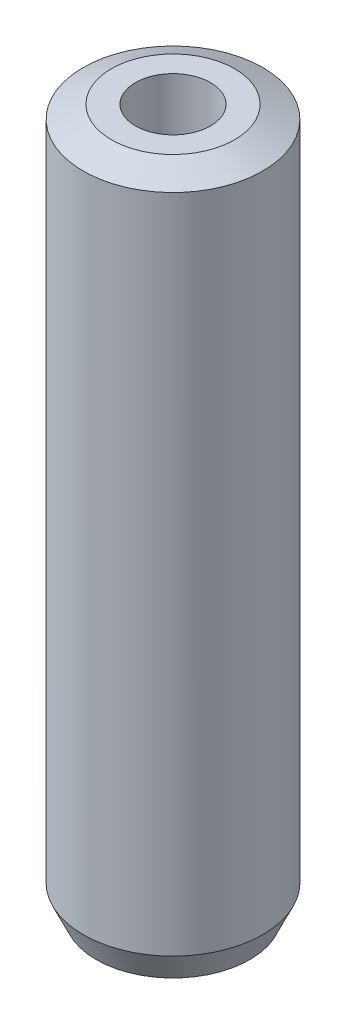
SolidWorks part; units mm, degrees
ref_plane "Front Plane" through (0, 0, 0) normal (0, 0, 1) x (1, 0, 0)
ref_plane "Top Plane" through (0, 0, 0) normal (0, 1, 0) x (1, 0, 0)
ref_plane "Right Plane" through (0, 0, 0) normal (1, 0, 0) x (0, 0, -1)
sketch "Sketch1" plane through (0, 0, 0) normal (0, 1, 0) x (1, 0, 0)
  circle A0 centre (0, 0) radius 40
  dimension "SHAFT_OD" = 80
extrude "Boss-Extrude1" add sketch "Sketch1" along normal blind 313.0678
sketch "Sketch2" plane through (0, 0, 0) normal (0, 1, 0) x (1, 0, 0)
  circle A0 centre (0, 0) radius 16.7353
  dimension "BORE_D" = 33.4705
extrude "Cut-Extrude1" cut sketch "Sketch2" along normal through all
chamfer "Chamfer1" distance 5.8005 angle 65.199 2 edges at (0, 313.0678, 40) (0, 0, 40) first distance on face at (0, 313.0678, 40) first distance on face at (0, 0, 16.7353)
